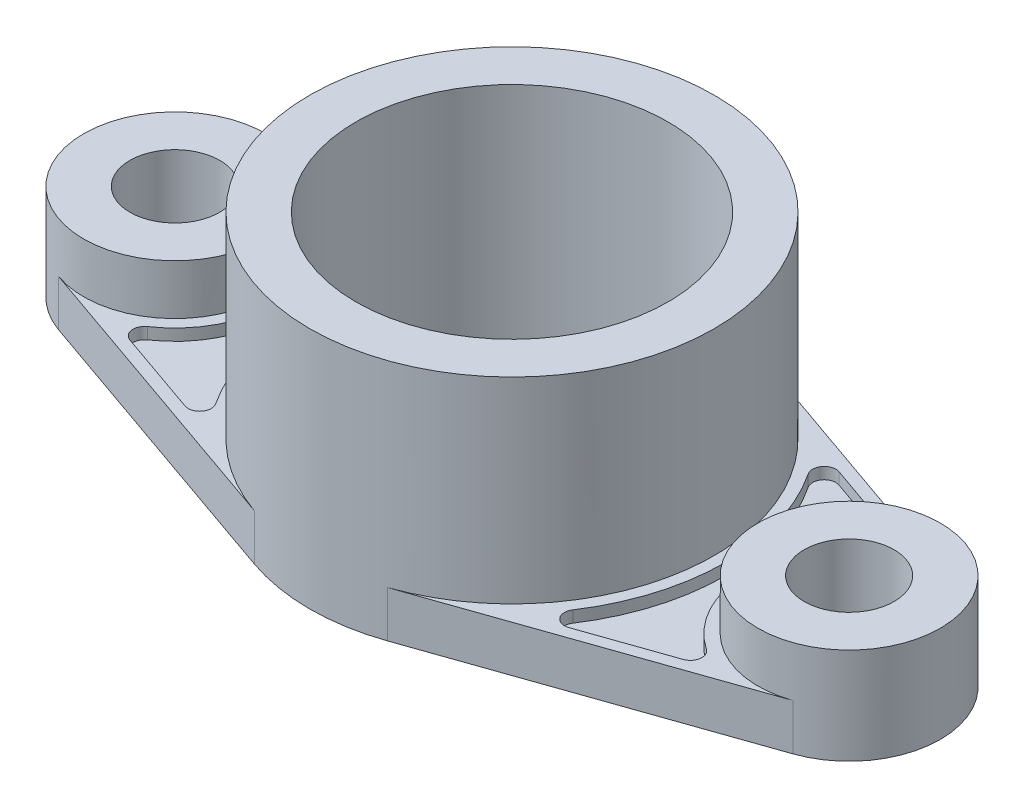
SolidWorks part; units mm, degrees
material "Polybutadiene (PB)"
ref_plane "Front Plane" through (0, 0, 0) normal (0, 0, 1) x (1, 0, 0)
ref_plane "Top Plane" through (0, 0, 0) normal (0, 1, 0) x (1, 0, 0)
ref_plane "Right Plane" through (0, 0, 0) normal (1, 0, 0) x (0, 0, -1)
sketch "Sketch1" plane through (0, 0, 0) normal (0, 1, 0) x (1, 0, 0)
  line L0 (17.3, 49.5677) -> (95.2987, 22.3448)
  line L1 (17.3, -49.5677) -> (95.2987, -22.3448)
  line L2 (0, 52.5) -> (0, -52.5) construction
  line L3 (-17.3, -49.5677) -> (-95.2987, -22.3448)
  line L4 (-17.3, 49.5677) -> (-95.2987, 22.3448)
  circle A1 centre (87.5, 0) radius 23.6667
  circle A2 centre (0, 0) radius 52.5
  circle A3 centre (0, 0) radius 40.5
  circle A4 centre (87.5, 0) radius 11.6667
  circle A5 centre (-87.5, 0) radius 11.6667
  circle A6 centre (-87.5, 0) radius 23.6667
extrude "Boss-Extrude1" add sketch "Sketch1" along normal blind 9 contours A6 A5 | L4 A6 L3 A2 | L2 A2 A3 | A2 L2 A3 | L0 A2 L1 A1 | A1 A4 region at (58.0849, 0, 0) region at (41.8476, 0, -29.7177) region at (106.2504, 0, -13.3154) region at (-1.1739, 0, -46.5) region at (-58.0849, 0, 0) region at (-74.1846, 0, -18.7504)
extrude "Boss-Extrude2" add sketch "Sketch1<5>" along normal blind 25 contours A6 A5 | A1 A4 region at (106.2504, 0, -13.3154) region at (-74.1846, 0, -18.7504)
sketch "Sketch1<5>" plane through (0, 0, 0) normal (0, 1, 0) x (1, 0, 0) same geometry as "Sketch1"
extrude "Boss-Extrude3" add sketch "Sketch1<4>" along normal offset from surface (63 mm away) 38 contours A2 L2 A3 | L2 A2 A3 region at (41.8476, 0, -29.7177) region at (-1.1739, 0, -46.5) up to face at (87.5, 25, 11.6667) offset beyond the face yes
sketch "Sketch1<4>" plane through (0, 0, 0) normal (0, 1, 0) x (1, 0, 0) same geometry as "Sketch1"
sketch "Sketch3" plane through (0, 9, 0) normal (0, 1, 0) x (1, 0, 0)
  line L5 (40.0093, -38.4643) -> (78.3991, -25.0656)
  line L8 (78.3991, 25.0656) -> (40.0093, 38.4643)
  line L9 (49.8253, -35.0384) -> (71.8085, -27.3658)
  line L10 (71.8085, 27.3658) -> (49.8253, 35.0384)
  line L24 (-40.0093, 38.4643) -> (-78.3991, 25.0656)
  line L26 (-78.3991, -25.0656) -> (-40.0093, -38.4643)
  line L27 (-49.8253, 35.0384) -> (-71.8085, 27.3658)
  line L28 (-71.8085, -27.3658) -> (-49.8253, -35.0384)
  line L29 (17.3, -49.5677) -> (95.2987, -22.3448)
  line L30 (95.2987, 22.3448) -> (17.3, 49.5677)
  line L31 (17.3, -49.5677) -> (95.2987, -22.3448)
  line L32 (95.2987, 22.3448) -> (17.3, 49.5677)
  line L33 (-17.3, 49.5677) -> (-95.2987, 22.3448)
  line L34 (-95.2987, -22.3448) -> (-17.3, -49.5677)
  line L35 (-17.3, 49.5677) -> (-95.2987, 22.3448)
  line L36 (-95.2987, -22.3448) -> (-17.3, -49.5677)
  arc A8 (40.0093, -38.4643) -> (40.0093, 38.4643) centre (0, 0) ccw
  arc A10 (78.3991, 25.0656) -> (78.3991, -25.0656) centre (87.5, 0) ccw
  arc A11 (46.3323, -30.5543) -> (46.3323, 30.5543) centre (0, 0) ccw
  arc A16 (72.5067, 22.0525) -> (72.5067, -22.0525) centre (87.5, 0) ccw
  arc A30 (-46.3323, -30.5543) -> (-49.8253, -35.0384) centre (-48.8368, -32.2059) cw
  arc A32 (-72.5067, -22.0525) -> (-71.8085, -27.3658) centre (-70.82, -24.5334) ccw
  arc A35 (-40.0093, 38.4643) -> (-40.0093, -38.4643) centre (0, 0) ccw
  arc A36 (-78.3991, -25.0656) -> (-78.3991, 25.0656) centre (-87.5, 0) ccw
  arc A37 (-46.3323, 30.5543) -> (-46.3323, -30.5543) centre (0, 0) ccw
  arc A38 (-72.5067, -22.0525) -> (-72.5067, 22.0525) centre (-87.5, 0) ccw
  arc A39 (-71.8085, 27.3658) -> (-72.5067, 22.0525) centre (-70.82, 24.5334) ccw
  arc A40 (-46.3323, 30.5543) -> (-49.8253, 35.0384) centre (-48.8368, 32.2059) ccw
  arc A41 (72.5067, 22.0525) -> (71.8085, 27.3658) centre (70.82, 24.5334) ccw
  arc A42 (46.3323, 30.5543) -> (49.8253, 35.0384) centre (48.8368, 32.2059) cw
  arc A43 (46.3323, -30.5543) -> (49.8253, -35.0384) centre (48.8368, -32.2059) ccw
  arc A44 (71.8085, -27.3658) -> (72.5067, -22.0525) centre (70.82, -24.5334) ccw
  arc A47 (17.3, -49.5677) -> (17.3, 49.5677) centre (0, 0) ccw
  arc A48 (95.2987, 22.3448) -> (95.2987, -22.3448) centre (87.5, 0) ccw
  arc A49 (17.3, -49.5677) -> (17.3, 49.5677) centre (0, 0) ccw
  arc A50 (95.2987, 22.3448) -> (95.2987, -22.3448) centre (87.5, 0) ccw
  arc A51 (-17.3, 49.5677) -> (-17.3, -49.5677) centre (0, 0) ccw
  arc A52 (-95.2987, -22.3448) -> (-95.2987, 22.3448) centre (-87.5, 0) ccw
  arc A53 (-17.3, 49.5677) -> (-17.3, -49.5677) centre (0, 0) ccw
  arc A54 (-95.2987, -22.3448) -> (-95.2987, 22.3448) centre (-87.5, 0) ccw
  dimension "D3" = 3
extrude "Boss-Extrude4" add sketch "Sketch3" along normal blind 3
equation "\"B\"= 12"
equation "\"D2@Sketch1\"=\"B\""
equation "\"D3@Sketch1\"=\"B\""
equation "\"A\"= 35"
equation "\"D1@Sketch1\"=\"A\"*5"
equation "\"D5@Sketch1\"=\"A\"*(2/3)"
equation "\"C\"= 3"
equation "\"D1@Boss-Extrude4\"=\"C\""
equation "\"D4@Sketch1\"=\"A\"*3"
equation "\"D3@Sketch3\"=\"C\""
equation "\"D1@Sketch3\"=\"C\""
equation "\"D2@Sketch3\"=\"C\""
